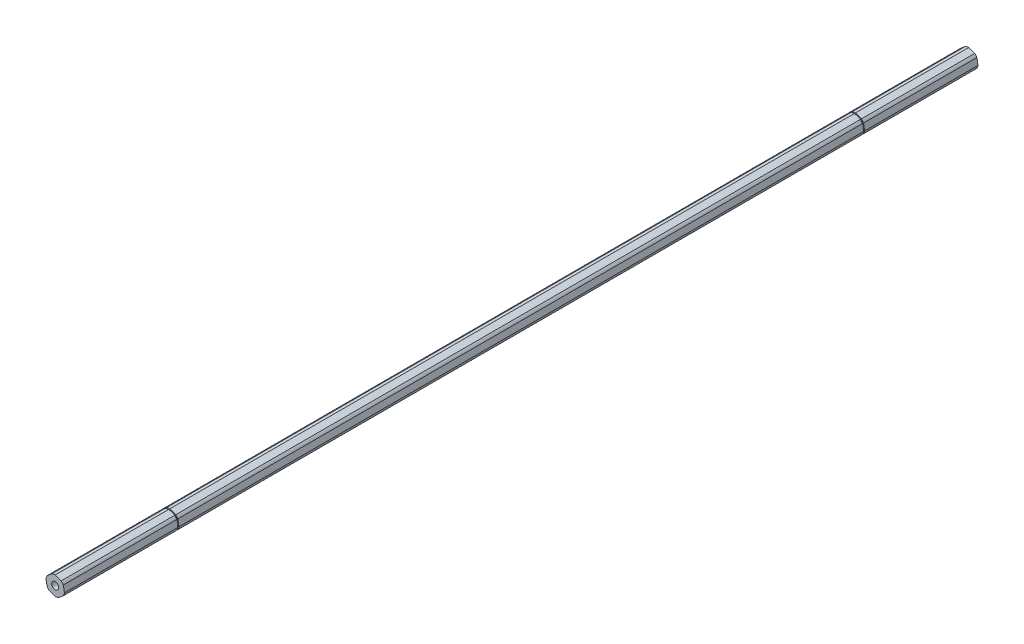
SolidWorks part; units mm, degrees
material "7075-T6 (SN)"
ref_plane "Front Plane" through (0, 0, 0) normal (0, 0, 1) x (1, 0, 0)
ref_plane "Top Plane" through (0, 0, 0) normal (0, 1, 0) x (1, 0, 0)
ref_plane "Right Plane" through (0, 0, 0) normal (1, 0, 0) x (0, 0, -1)
sketch "Sketch1" plane through (0, 0, 0) normal (0, 0, 1) x (1, 0, 0)
  line L1 (-6.6545, 1.1312) -> (-5.8457, -3.375)
  line L2 (-4.3069, -5.1974) -> (0, -6.75)
  line L3 (2.3476, -6.3286) -> (5.8457, -3.375)
  line L4 (6.6545, -1.1312) -> (5.8457, 3.375)
  line L5 (4.3069, 5.1974) -> (0, 6.75)
  line L6 (-2.3476, 6.3286) -> (-5.8457, 3.375)
  circle A0 centre (0, 0) radius 6.35 construction
  arc A1 (-5.8457, 3.375) -> (-6.6545, 1.1312) centre (0, 0) ccw
  arc A2 (-5.8457, -3.375) -> (-4.3069, -5.1974) centre (0, 0) ccw
  arc A3 (0, -6.75) -> (2.3476, -6.3286) centre (0, 0) ccw
  arc A4 (5.8457, -3.375) -> (6.6545, -1.1312) centre (0, 0) ccw
  arc A5 (5.8457, 3.375) -> (4.3069, 5.1974) centre (0, 0) ccw
  arc A6 (0, 6.75) -> (-2.3476, 6.3286) centre (0, 0) ccw
  dimension "D1" = 12.7
  dimension "D2" = 13.5
extrude "Boss-Extrude1" add sketch "Sketch1" along normal mid plane 658.9014
sketch "Sketch2" plane through (0, 0, 329.4507) normal (0, 0, 1) x (1, 0, 0)
  circle A0 centre (0, 0) radius 2.0193
  dimension "D1" = 4.0386
extrude "Cut-Extrude1" cut sketch "Sketch2" against normal through all
hole_wizard "1/4-20 Tapped Hole1" positions "Sketch5" profile "Sketch6" tap size "1/4-20" standard "ANSI Inch"
sketch "Sketch5" plane through (0, 0, 329.4507) normal (0, 0, 1) x (1, 0, 0)
  point P0 (0, 0)
sketch "Sketch6" plane through (0, 0, 329.4507) normal (1, 0, 0) x (0, -1, 0)
  line L0 (0, 0) -> (0, 20.5838)
  line L1 (0, 20.5838) -> (2.5527, 19.05)
  line L2 (2.5527, 19.05) -> (2.5527, 0)
  line L5 (2.5527, 0) -> (0, 0)
  line L10 (0, 20.5838) -> (-2.5527, 19.05) construction
  line L11 (0, -6.35) -> (0, 107.95) construction
  dimension "Tap Drill Dia." = 5.1054
  dimension "Tap Drill Depth" = 19.05
  dimension "Drill Angle" = 118
cosmetic thread "Hole Thread1" parameters "D1"=12.7, "D2"=6.35
hole_wizard "1/4-20 Tapped Hole2" positions "Sketch7" profile "Sketch8" tap size "1/4-20" standard "ANSI Inch"
sketch "Sketch7" plane through (0, 0, -329.4507) normal (0, 0, -1) x (-1, 0, 0)
  point P0 (0, 0)
sketch "Sketch8" plane through (0, 0, -329.4507) normal (1, 0, 0) x (0, 1, 0)
  line L0 (0, 0) -> (0, 20.5838)
  line L1 (0, 20.5838) -> (2.5527, 19.05)
  line L2 (2.5527, 19.05) -> (2.5527, 0)
  line L5 (2.5527, 0) -> (0, 0)
  line L10 (0, 20.5838) -> (-2.5527, 19.05) construction
  line L11 (0, -6.35) -> (0, 107.95) construction
  dimension "Tap Drill Dia." = 5.1054
  dimension "Tap Drill Depth" = 19.05
  dimension "Drill Angle" = 118
cosmetic thread "Hole Thread2" parameters "D1"=12.7, "D2"=6.35
sketch "Sketch11" plane through (0, 0, 0) normal (0, 1, 0) x (1, 0, 0)
  line L0 (0, 0) -> (0, -329.4507) construction
sketch "Sketch10" plane through (0, 0.5654, 0) normal (1, 0, 0) x (0, 0, -1)
  line L0 (-329.4507, 6.1846) -> (329.4507, 6.1846) construction
  line L1 (246.8245, 6.1846) -> (247.7135, 6.1846)
  line L2 (246.8245, 6.1846) -> (246.8245, 5.3782)
  line L3 (246.8245, 5.3782) -> (247.7135, 5.3782)
  line L4 (247.7135, 6.1846) -> (247.7135, 5.3782)
  line L5 (246.8245, 6.1846) -> (247.7135, 5.3782) construction
  line L6 (246.8245, 5.3782) -> (247.7135, 6.1846) construction
  line L8 (329.4507, 4.632) -> (329.4507, 6.1846) construction
  point P4 (247.269, 5.7814)
  dimension "D1" = 0.889
  dimension "D2" = 5.9436
  dimension "D3" = 81.7372
revolve "Cut-Revolve1" cut sketch "Sketch10" angle 360 about L0
mirror "Mirror1" about plane through (0, 0, 0) normal (0, 0, 1) of "Cut-Revolve1"
